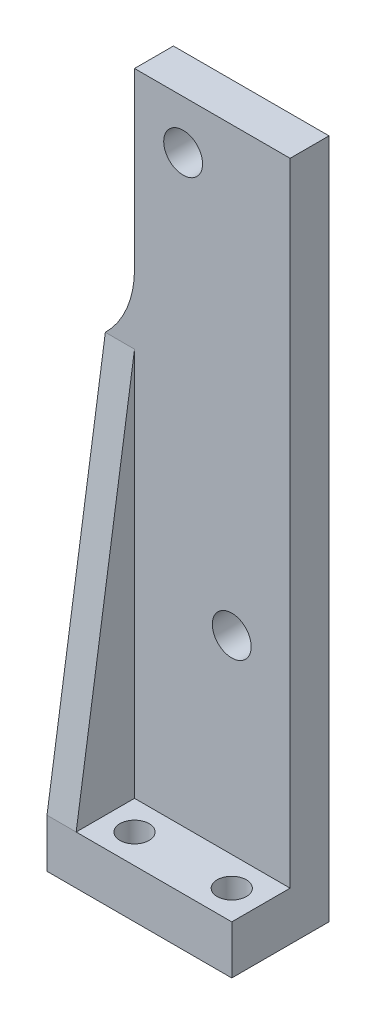
SolidWorks part; units mm, degrees
ref_plane "前视基准面" through (0, 0, 0) normal (0, 0, 1) x (1, 0, 0)
ref_plane "上视基准面" through (0, 0, 0) normal (0, 1, 0) x (1, 0, 0)
ref_plane "右视基准面" through (0, 0, 0) normal (1, 0, 0) x (0, 0, -1)
sketch "草图1" plane through (0, 0, 0) normal (0, 1, 0) x (1, 0, 0)
  line L0 (-10, 0) -> (-7, 0)
  line L1 (-10, 3) -> (6, 3)
  line L2 (-10, 3) -> (-10, -3)
  line L3 (-10, -3) -> (6, -3)
  line L4 (6, 3) -> (6, -3)
  line L5 (-10, 3) -> (6, -3) construction
  line L6 (-10, -3) -> (6, 3) construction
  line L7 (6, 0) -> (3, 0)
  circle A5 centre (-7, 0) radius 1.5
  circle A6 centre (3, 0) radius 1.5
extrude "凸台-拉伸1" add sketch "草图1" along normal blind 5 contours L7 L4 L1 L2 L0 | L0 L2 L3 L4 L7 region at (-2, 0, 0)
sketch "草图2" plane through (0, 0, -3) normal (0, 0, -1) x (-1, 0, 0)
  line L0 (-6, 0) -> (-6, 70)
  line L1 (-6, 70) -> (10, 70)
  line L2 (10, 70) -> (10, 0)
  line L3 (10, 0) -> (-6, 0)
extrude "凸台-拉伸2" add sketch "草图2" along normal blind 4 contours L0 L1 L2 L3
sketch "草图3" plane through (0, 0, -7) normal (0, 0, -1) x (-1, 0, 0)
  circle A0 centre (5, 65) radius 2
extrude "切除-拉伸1" cut sketch "草图3" against normal through all contours A0
sketch "草图4" plane through (0, 0, -7) normal (0, 0, -1) x (-1, 0, 0)
  line L0 (0, 0) -> (0, 24.5)
  circle A0 centre (0, 24.5) radius 2
extrude "切除-拉伸2" cut sketch "草图4" against normal through all contours A0
sketch "草图5" plane through (0, 0, -7) normal (0, 0, -1) x (-1, 0, 0)
  circle A0 centre (5, 65) radius 3.5
extrude "切除-拉伸3" cut sketch "草图5" against normal blind 1
sketch "草图6" plane through (-10, 0, 0) normal (-1, 0, 0) x (0, 0, 1)
  line L0 (-3, 5) -> (-3, 45)
  line L1 (-3, 70) -> (-3, 5) construction
  line L2 (-3, 45) -> (-7, 45)
  line L3 (-7, 70) -> (-7, 0) construction
  line L4 (-7, 45) -> (-7, 0)
  line L5 (-7, 0) -> (3, 0)
  line L6 (3, 0) -> (3, 5)
  line L7 (3, 5) -> (-3, 45)
  line M1 (-7, 0) -> (3, 0)
  line M2 (3, 0) -> (3, 5)
  line M3 (3, 5) -> (-3, 5)
  line M4 (-3, 5) -> (-3, 70)
  line M6 (-7, 70) -> (-7, 0)
extrude "凸台-拉伸3" add sketch "草图6" along normal blind 3 contours L7 M3 M4 | L2 M4 M6 M1 M2 M3 region at (-10, 19.6429, -4.2857) region at (-10, 18.3333, -1)
fillet "圆角1" radius 10 1 edges at (-10, 45, -5)
